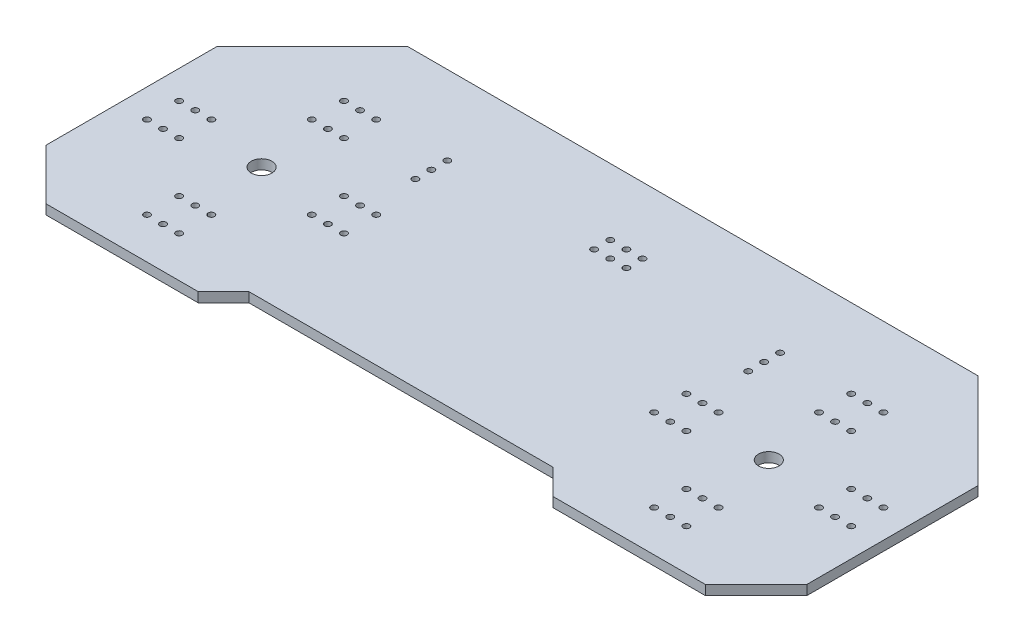
SolidWorks part; units mm, degrees
ref_plane "Front Plane" through (0, 0, 0) normal (0, 0, 1) x (1, 0, 0)
ref_plane "Top Plane" through (0, 0, 0) normal (0, 1, 0) x (1, 0, 0)
ref_plane "Right Plane" through (0, 0, 0) normal (1, 0, 0) x (0, 0, -1)
sketch "Sketch1" plane through (0, 0, 0) normal (0, 1, 0) x (1, 0, 0)
  line L0 (0, 0) -> (0, 13) construction
  line L1 (-60, -22) -> (60, -22)
  line L2 (-60, -22) -> (-60, 28)
  line L3 (-60, 28) -> (60, 28)
  line L4 (60, -22) -> (60, 28)
  line L5 (0, 0) -> (60, 28) construction
  line L6 (-60, 28) -> (0, 0) construction
  line L11 (0, 13) -> (0, 28) construction
  point P0 (0, 0)
  dimension "D1" = 120
  dimension "D2" = 28
  dimension "D6" = 22
extrude "Boss-Extrude1" add sketch "Sketch1" along normal blind 1.53
sketch "Sketch2" plane through (0, 1.53, 0) normal (0, 1, 0) x (1, 0, 0)
  line L0 (-55.54, 2.54) -> (-53, 2.54) construction
  line L1 (-53, 2.54) -> (-50.46, 2.54) construction
  line L2 (-53, 2.54) -> (-53, -2.54) construction
  line L3 (-53, -2.54) -> (-50.46, -2.54) construction
  line L4 (-53, -2.54) -> (-55.54, -2.54) construction
  line L5 (-53, 0) -> (-27, 0) construction
  line L6 (-29.54, 2.54) -> (-27, 2.54) construction
  line L7 (-27, 2.54) -> (-24.46, 2.54) construction
  line L8 (-27, 2.54) -> (-27, -2.54) construction
  line L9 (-27, -2.54) -> (-24.46, -2.54) construction
  line L10 (-27, -2.54) -> (-29.54, -2.54) construction
  line L11 (-42.54, 15.54) -> (-40, 15.54) construction
  line L12 (-40, 15.54) -> (-37.46, 15.54) construction
  line L13 (-40, 15.54) -> (-40, 10.46) construction
  line L14 (-40, 10.46) -> (-37.46, 10.46) construction
  line L15 (-40, 10.46) -> (-42.54, 10.46) construction
  line L16 (-42.54, -10.46) -> (-40, -10.46) construction
  line L17 (-40, -10.46) -> (-37.46, -10.46) construction
  line L18 (-40, -10.46) -> (-40, -15.54) construction
  line L19 (-40, -15.54) -> (-37.46, -15.54) construction
  line L20 (-40, -15.54) -> (-42.54, -15.54) construction
  line L21 (-40, -13) -> (-40, 0) construction
  line L22 (-40, 0) -> (-40, 13) construction
  line L23 (-27, 0) -> (0, 0) construction
  circle A0 centre (-55.54, 2.54) radius 0.5
  circle A1 centre (-53, 2.54) radius 0.5
  circle A2 centre (-50.46, 2.54) radius 0.5
  circle A3 centre (-55.54, -2.54) radius 0.5
  circle A4 centre (-53, -2.54) radius 0.5
  circle A5 centre (-50.46, -2.54) radius 0.5
  circle A6 centre (-29.54, 2.54) radius 0.5
  circle A7 centre (-27, 2.54) radius 0.5
  circle A8 centre (-24.46, 2.54) radius 0.5
  circle A9 centre (-29.54, -2.54) radius 0.5
  circle A10 centre (-27, -2.54) radius 0.5
  circle A11 centre (-24.46, -2.54) radius 0.5
  circle A12 centre (-42.54, 15.54) radius 0.5
  circle A13 centre (-40, 15.54) radius 0.5
  circle A14 centre (-37.46, 15.54) radius 0.5
  circle A15 centre (-42.54, 10.46) radius 0.5
  circle A16 centre (-40, 10.46) radius 0.5
  circle A17 centre (-37.46, 10.46) radius 0.5
  circle A18 centre (-42.54, -10.46) radius 0.5
  circle A19 centre (-40, -10.46) radius 0.5
  circle A20 centre (-37.46, -10.46) radius 0.5
  circle A21 centre (-42.54, -15.54) radius 0.5
  circle A22 centre (-40, -15.54) radius 0.5
  circle A23 centre (-37.46, -15.54) radius 0.5
  circle A24 centre (-40, 0) radius 1.625
  point P15 (-27, 0)
  dimension "D1" = 1
  dimension "D7" = 3.25
  dimension "D2" = 2.54
  dimension "D3" = 5.08
  dimension "D4" = 26
  dimension "D5" = 26
  dimension "D6" = 40
extrude "Cut-Extrude1" cut sketch "Sketch2" against normal through all
mirror "Mirror1" about plane through (0, 0, 0) normal (1, 0, 0) of "Cut-Extrude1"
sketch "Sketch5" plane through (0, 1.53, 0) normal (0, 1, 0) x (1, 0, 0)
  line L0 (-2.54, 17.54) -> (0, 17.54) construction
  line L1 (0, 17.54) -> (2.54, 17.54) construction
  line L2 (0, 17.54) -> (0, 15) construction
  line L3 (0, 15) -> (2.54, 15) construction
  line L4 (0, 15) -> (-2.54, 15) construction
  line L5 (0, 0) -> (0, 15) construction
  circle A0 centre (-2.54, 17.54) radius 0.5
  circle A1 centre (0, 17.54) radius 0.5
  circle A2 centre (2.54, 17.54) radius 0.5
  circle A3 centre (-2.54, 15) radius 0.5
  circle A4 centre (0, 15) radius 0.5
  circle A5 centre (2.54, 15) radius 0.5
  dimension "D1" = 2.54
  dimension "D2" = 2.54
  dimension "D3" = 15
extrude "Cut-Extrude2" cut sketch "Sketch5" against normal through all
sketch "Sketch6" plane through (0, 1.53, 0) normal (0, 1, 0) x (1, 0, 0)
  line L0 (-45, 28) -> (-60, 13)
  line L1 (60, 28) -> (-60, 28) construction
  line L2 (-60, 28) -> (-60, -22) construction
  line L3 (-60, 13) -> (-60, -14)
  line L4 (-60, -14) -> (-52, -22)
  line L5 (-60, -22) -> (60, -22) construction
  line L6 (-52, -22) -> (-28, -22)
  line L7 (-28, -22) -> (-24, -18)
  line L8 (-24, -18) -> (24, -18)
  line L9 (24, -18) -> (28, -22)
  line L10 (28, -22) -> (52, -22)
  line L11 (52, -22) -> (60, -14)
  line L12 (60, -22) -> (60, 28) construction
  line L13 (60, -14) -> (60, 13)
  line L14 (60, 13) -> (45, 28)
  line L15 (45, 28) -> (-45, 28)
  line L16 (0, 0) -> (0, -18) construction
  line L17 (0, 0) -> (0, 28) construction
  line L19 (-70.5255, -34.7658) -> (70.5255, -34.7658)
  line L20 (-70.5255, -34.7658) -> (-70.5255, 34.7658)
  line L21 (-70.5255, 34.7658) -> (70.5255, 34.7658)
  line L22 (70.5255, -34.7658) -> (70.5255, 34.7658)
  line L23 (-70.5255, -34.7658) -> (70.5255, 34.7658) construction
  line L24 (-70.5255, 34.7658) -> (70.5255, -34.7658) construction
  dimension "D1" = 45
  dimension "D2" = 45
  dimension "D3" = 90
  dimension "D4" = 14
  dimension "D5" = 18
  dimension "D6" = 24
extrude "Cut-Extrude4" cut sketch "Sketch6" against normal through all
sketch "Sketch7" plane through (0, 1.53, 0) normal (0, 1, 0) x (1, 0, 0)
  line L0 (-26.25, 15.54) -> (-26.25, 13.02) construction
  line L1 (-26.25, 13.02) -> (-26.25, 10.5) construction
  line L2 (-26.25, 10.5) -> (-26.25, 0) construction
  line L3 (-26.25, 0) -> (0, 0) construction
  line L4 (0, 0.353) -> (0, 11.8498) construction
  line L5 (26.25, 13.02) -> (26.25, 10.5) construction
  line L6 (26.25, 15.54) -> (26.25, 13.02) construction
  circle A0 centre (-26.25, 15.54) radius 0.5
  circle A1 centre (-26.25, 13.02) radius 0.5
  circle A2 centre (-26.25, 10.5) radius 0.5
  circle A3 centre (26.25, 10.5) radius 0.5
  circle A4 centre (26.25, 13.02) radius 0.5
  circle A5 centre (26.25, 15.54) radius 0.5
  dimension "D1" = 1
  dimension "D2" = 5.04
  dimension "D3" = 26.25
  dimension "D4" = 10.5
extrude "Cut-Extrude5" cut sketch "Sketch7" against normal through all
